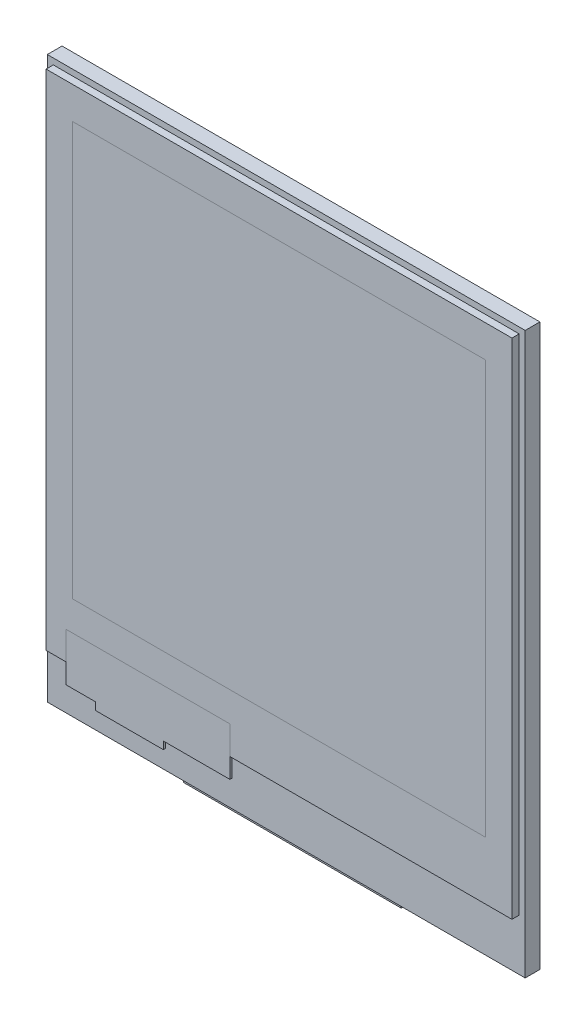
SolidWorks part; units mm, degrees
ref_plane "Front Plane" through (0, 0, 0) normal (0, 0, 1) x (1, 0, 0)
ref_plane "Top Plane" through (0, 0, 0) normal (0, 1, 0) x (1, 0, 0)
ref_plane "Right Plane" through (0, 0, 0) normal (1, 0, 0) x (0, 0, -1)
sketch "Sketch1" plane through (0, 0, 0) normal (0, 0, 1) x (1, 0, 0)
  line L1 (-15.9, 18.66) -> (15.9, 18.66)
  line L2 (-15.9, 18.66) -> (-15.9, -18.66)
  line L3 (-15.9, -18.66) -> (15.9, -18.66)
  line L4 (15.9, 18.66) -> (15.9, -18.66)
  line L5 (-15.9, 18.66) -> (15.9, -18.66) construction
  line L6 (-15.9, -18.66) -> (15.9, 18.66) construction
  point P0 (0, 0)
  dimension "D1" = 31.8
  dimension "D2" = 37.32
extrude "Boss-Extrude1" add sketch "Sketch1" along normal blind 0.98
sketch "Sketch2" plane through (0, 0, 0.98) normal (0, 0, 1) x (1, 0, 0)
  line L0 (0, 18.26) -> (0, 1.0637)
  line L1 (-15.5, 18.26) -> (15.5, 18.26)
  line L2 (-15.5, 18.26) -> (-15.5, -15.24)
  line L3 (-15.5, -15.24) -> (15.5, -15.24)
  line L4 (15.5, 18.26) -> (15.5, -15.24)
  line L5 (15.9, 18.66) -> (-15.9, 18.66) construction
  dimension "D1" = 31
  dimension "D2" = 33.5
  dimension "D3" = 0.4
extrude "Boss-Extrude2" add sketch "Sketch2" along normal blind 1.46 from surface contours L4 L1 L2 L3 region at (-7.75, 17.8036, 0.98) starting at face at (0, 0, 0)
sketch "Sketch3" plane through (0, 0, 1.46) normal (0, 0, 1) x (1, 0, 0)
  line L0 (-14.17, -15.24) -> (-14.17, -16.56)
  line L1 (15.5, -15.24) -> (-15.5, -15.24) construction
  line L2 (-14.17, -16.56) -> (-12.2, -16.56)
  line L3 (-12.2, -16.56) -> (-12.2, -17.06)
  line L4 (-12.2, -17.06) -> (-7.7, -17.06)
  line L5 (-7.7, -17.06) -> (-7.7, -16.56)
  line L6 (-7.7, -16.56) -> (-3.27, -16.56)
  line L7 (-3.27, -16.56) -> (-3.27, -15.24)
  line L8 (-15.5, -15.24) -> (15.5, -15.24) construction
  line L9 (-15.5, -15.24) -> (-15.5, 18.26) construction
  line L10 (-15.9, 18.66) -> (-15.9, -18.66) construction
  line L11 (-15.9, -18.66) -> (15.9, -18.66) construction
  line L12 (-14.17, -15.24) -> (-3.27, -15.24)
  dimension "D1" = 10.9
  dimension "D2" = 1.33
  dimension "D3" = 3.7
  dimension "D4" = 4.5
  dimension "D5" = 2.1
  dimension "D6" = 0.5
extrude "Boss-Extrude3" add sketch "Sketch3" against normal blind 0.15
sketch "Sketch4" plane through (0, 0, 0.98) normal (0, 0, 1) x (1, 0, 0)
  line L0 (-15.9, -18.66) -> (15.9, -18.66) construction
  line L1 (-7.25, -18.66) -> (7.25, -18.66)
  line L2 (-7.25, -18.66) -> (-7.25, -19.16)
  line L3 (-7.25, -19.16) -> (7.25, -19.16)
  line L4 (7.25, -18.66) -> (7.25, -19.16)
  line L5 (0, -18.66) -> (0, 0) construction
  dimension "D1" = 14.5
  dimension "D2" = 0.5
extrude "Boss-Extrude4" add sketch "Sketch4" against normal blind 0.15 from offset 0.4 contours L2 L1 L4 L3 offset against normal yes
sketch "Sketch5" plane through (0, 0, 1.46) normal (0, 0, 1) x (1, 0, 0)
  line L0 (0, 2.365) -> (0, 0) construction
  line L1 (13.755, -11.39) -> (-13.755, -11.39)
  line L2 (13.755, -11.39) -> (13.755, 16.12)
  line L3 (13.755, 16.12) -> (-13.755, 16.12)
  line L4 (-13.755, -11.39) -> (-13.755, 16.12)
  line L5 (13.755, -11.39) -> (-13.755, 16.12) construction
  line L6 (13.755, 16.12) -> (-13.755, -11.39) construction
  line L7 (15.5, 18.26) -> (-15.5, 18.26) construction
  point P0 (0, 2.365)
  dimension "D1" = 27.51
  dimension "D2" = 2.14
wrap "Wrap1" sketch "Sketch5" wrap type scribe source sketch "Sketch5"
sketch "Sketch6" plane through (0, 0, 1.46) normal (0, 0, 1) x (1, 0, 0)
  line L0 (-14.17, -15.24) -> (-14.17, -13.36)
  line L1 (-14.17, -13.36) -> (-3.27, -13.36)
  line L2 (-3.27, -13.36) -> (-3.27, -15.24)
  line L3 (-3.27, -16.56) -> (-3.27, -15.24) construction
  line L4 (-7.7, -16.56) -> (-3.27, -16.56) construction
  line L5 (-7.7, -17.06) -> (-7.7, -16.56) construction
  line L6 (-12.2, -17.06) -> (-7.7, -17.06) construction
  line L7 (-12.2, -16.56) -> (-12.2, -17.06) construction
  line L8 (-14.17, -16.56) -> (-12.2, -16.56) construction
  line L9 (-14.17, -15.24) -> (-14.17, -16.56) construction
  line L10 (-3.27, -16.56) -> (-3.27, -15.24)
  line L11 (-7.7, -16.56) -> (-3.27, -16.56)
  line L12 (-7.7, -17.06) -> (-7.7, -16.56)
  line L13 (-12.2, -17.06) -> (-7.7, -17.06)
  line L14 (-12.2, -16.56) -> (-12.2, -17.06)
  line L15 (-14.17, -16.56) -> (-12.2, -16.56)
  line L16 (-14.17, -15.24) -> (-14.17, -16.56)
  dimension "D1" = 3.2
wrap "Wrap2" sketch "Sketch6" wrap type scribe source sketch "Sketch6"
